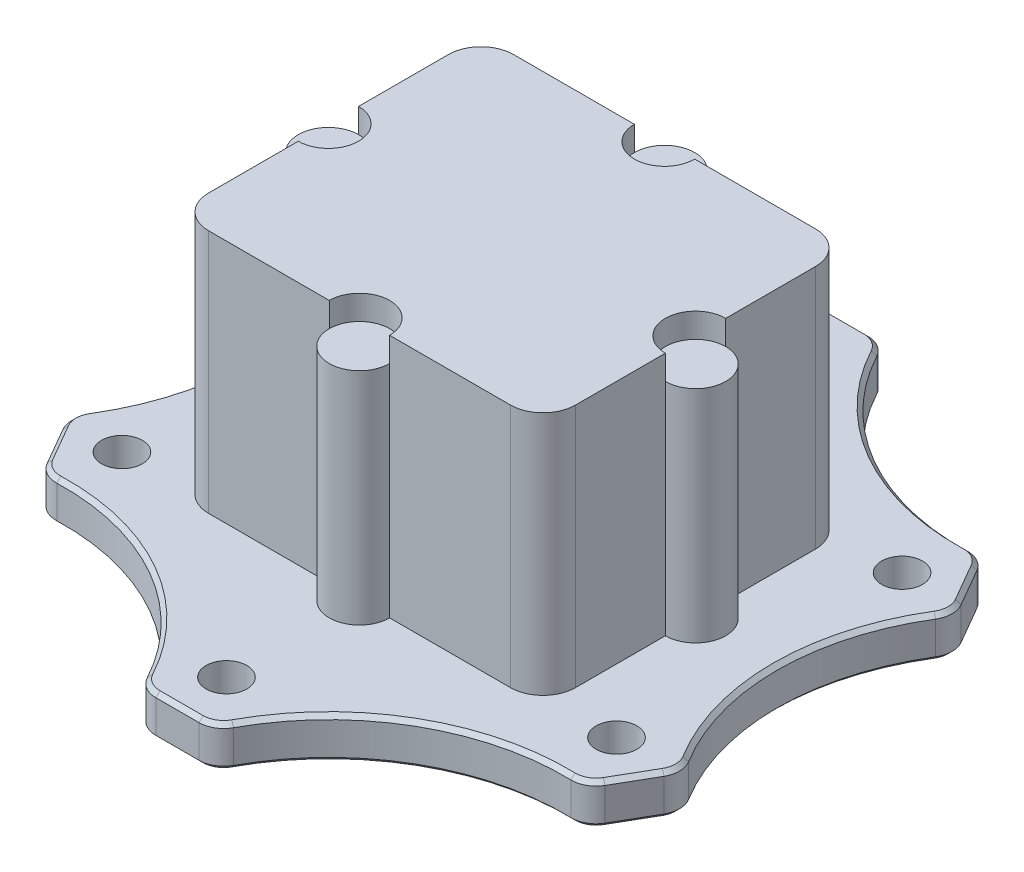
SolidWorks part; units mm, degrees
ref_plane "Front Plane" through (0, 0, 0) normal (0, 0, 1) x (1, 0, 0)
ref_plane "Top Plane" through (0, 0, 0) normal (0, 1, 0) x (1, 0, 0)
ref_plane "Right Plane" through (0, 0, 0) normal (1, 0, 0) x (0, 0, -1)
ref_plane "Plane1" through (0, 227, 0) normal (0, -1, 0) x (1, 0, 0)
sketch "Sketch1" plane through (0, 227, 0) normal (0, -1, 0) x (1, 0, 0)
  line L0 (610.4723, 48.998) -> (619.4723, 48.998)
  line L1 (648.2294, 65.6009) -> (652.7294, 73.3951)
  line L2 (652.7294, 106.6009) -> (648.2294, 114.3951)
  line L3 (619.4723, 130.998) -> (610.4723, 130.998)
  line L4 (581.7153, 114.3951) -> (577.2153, 106.6009)
  line L5 (577.2153, 73.3951) -> (581.7153, 65.6009)
  arc A0 (581.7153, 65.6009) -> (610.4723, 48.998) centre (584.2992, 36.8706) cw
  arc A1 (619.4723, 48.998) -> (648.2294, 65.6009) centre (645.6455, 36.8706) cw
  arc A2 (652.7294, 73.3951) -> (652.7294, 106.6009) centre (676.3186, 89.998) cw
  arc A3 (648.2294, 114.3951) -> (619.4723, 130.998) centre (645.6455, 143.1255) cw
  arc A4 (610.4723, 130.998) -> (581.7153, 114.3951) centre (584.2992, 143.1255) cw
  arc A5 (577.2153, 106.6009) -> (577.2153, 73.3951) centre (553.626, 89.998) cw
extrude "Boss-Extrude1" add sketch "Sketch1" against normal blind 5
hole_wizard "#10 Clearance Hole1" positions "Sketch3" profile "Sketch2" hole size "#10" standard "ANSI Inch"
sketch "Sketch3" plane through (0, 232, 0) normal (0, 1, 0) x (1, 0, 0)
  point P0 (614.9723, -124.998)
  point P1 (584.6614, -72.498)
  point P2 (584.6614, -107.498)
  point P3 (614.9723, -54.998)
  point P4 (645.2832, -107.498)
  point P5 (645.2832, -72.498)
sketch "Sketch2" plane through (614.9723, 232, 124.998) normal (1, 0, 0) x (0, 0, 1)
  line L0 (0, 0) -> (0, 5)
  line L1 (0, 5) -> (2.5, 5)
  line L2 (2.5, 5) -> (2.5, 0)
  line L5 (2.5, 0) -> (0, 0)
  line L11 (0, -6.35) -> (0, 107.95) construction
  dimension "Thru Hole Dia." = 5
  dimension "Thru Hole Depth" = 5
fillet "Fillet1" radius 3 12 edges at (652.7294, 229.5, 106.6009) (577.2153, 229.5, 106.6009) (581.7153, 229.5, 65.6009) (648.2294, 229.5, 65.6009) (652.7294, 229.5, 73.3951) (619.4723, 229.5, 130.998) (648.2294, 229.5, 114.3951) (619.4723, 229.5, 48.998) (577.2153, 229.5, 73.3951) (610.4723, 229.5, 48.998) (610.4723, 229.5, 130.998) (581.7153, 229.5, 114.3951) tangent propagation no
chamfer "Chamfer1" distance 0.5 angle 45 48 edges at (648.0194, 232, 66.0846) (650.4794, 232, 69.498) (631.2223, 232, 61.8522) (652.2055, 232, 73.3351) (619.1585, 232, 49.4217) (647.4723, 232, 89.998) (614.9723, 232, 48.998) (652.2055, 232, 106.6609) (610.7862, 232, 49.4217) (650.4794, 232, 110.498) (598.7223, 232, 61.8522) (648.0194, 232, 113.9115) (581.9252, 232, 66.0846) (631.2223, 232, 118.1438) (579.4653, 232, 69.498) (619.1585, 232, 130.5744) (577.7391, 232, 73.3351) (614.9723, 232, 130.998) (582.4723, 232, 89.998) (610.7862, 232, 130.5744) (577.7391, 232, 106.6609) (598.7223, 232, 118.1438) (579.4653, 232, 110.498) (581.9252, 232, 113.9115) (631.2223, 227, 118.1438) (619.1585, 227, 130.5744) (648.0194, 227, 113.9115) (614.9723, 227, 130.998) (650.4794, 227, 110.498) (610.7862, 227, 130.5744) (652.2055, 227, 106.6609) (598.7223, 227, 118.1438) (647.4723, 227, 89.998) (581.9252, 227, 113.9115) (652.2055, 227, 73.3351) (579.4653, 227, 110.498) (650.4794, 227, 69.498) (577.7391, 227, 106.6609) (648.0194, 227, 66.0846) (582.4723, 227, 89.998) (631.2223, 227, 61.8522) (577.7391, 227, 73.3351) (619.1585, 227, 49.4217) (579.4653, 227, 69.498) (614.9723, 227, 48.998) (581.9252, 227, 66.0846) (610.7862, 227, 49.4217) (598.7223, 227, 61.8522)
sketch "Sketch4" plane through (0, 232, 0) normal (0, 1, 0) x (1, 0, 0)
  line L0 (614.9723, -54.998) -> (614.9723, -124.998) construction
  line L1 (584.6614, -107.498) -> (645.2832, -72.498) construction
  line L3 (596.4723, -108.698) -> (633.4723, -108.698)
  line L4 (592.4723, -104.698) -> (592.4723, -75.298)
  line L5 (596.4723, -71.298) -> (633.4723, -71.298)
  line L6 (637.4723, -104.698) -> (637.4723, -75.298)
  line L7 (592.4723, -108.698) -> (637.4723, -71.298) construction
  line L8 (592.4723, -71.298) -> (637.4723, -108.698) construction
  arc A0 (596.4723, -108.698) -> (592.4723, -104.698) centre (596.4723, -104.698) cw
  arc A1 (633.4723, -108.698) -> (637.4723, -104.698) centre (633.4723, -104.698) ccw
  arc A2 (633.4723, -71.298) -> (637.4723, -75.298) centre (633.4723, -75.298) cw
  arc A3 (592.4723, -75.298) -> (596.4723, -71.298) centre (596.4723, -75.298) cw
  circle A4 centre (614.9723, -71.298) radius 3.7
  circle A5 centre (592.4723, -89.998) radius 3.7
  circle A6 centre (614.9723, -108.698) radius 3.7
  circle A7 centre (637.4723, -89.998) radius 3.7
  point P8 (614.9723, -89.998)
  dimension "D3" = 4
  dimension "D4" = 7.4
  dimension "D1" = 45
  dimension "D2" = 37.4
extrude "Boss-Extrude4" add sketch "Sketch4" along normal blind 30 contours A7 L6 A2 L5 A4 A3 L4 A5 A0 L3 A6 A1 region at (614.9723, 232, 89.998)
sketch "Sketch5" plane through (0, 232, 0) normal (0, 1, 0) x (1, 0, 0)
  line L0 (637.4723, -104.698) -> (637.4723, -75.298) construction
  line L1 (596.4723, -108.698) -> (633.4723, -108.698) construction
  circle A4 centre (614.9723, -71.298) radius 3.7
  circle A5 centre (637.4723, -89.998) radius 3.7
  circle A6 centre (614.9723, -108.698) radius 3.7
  circle A7 centre (592.4723, -89.998) radius 3.7
extrude "Boss-Extrude5" add sketch "Sketch5" along normal blind 27 contours A7 | A4 | A5 | A6
